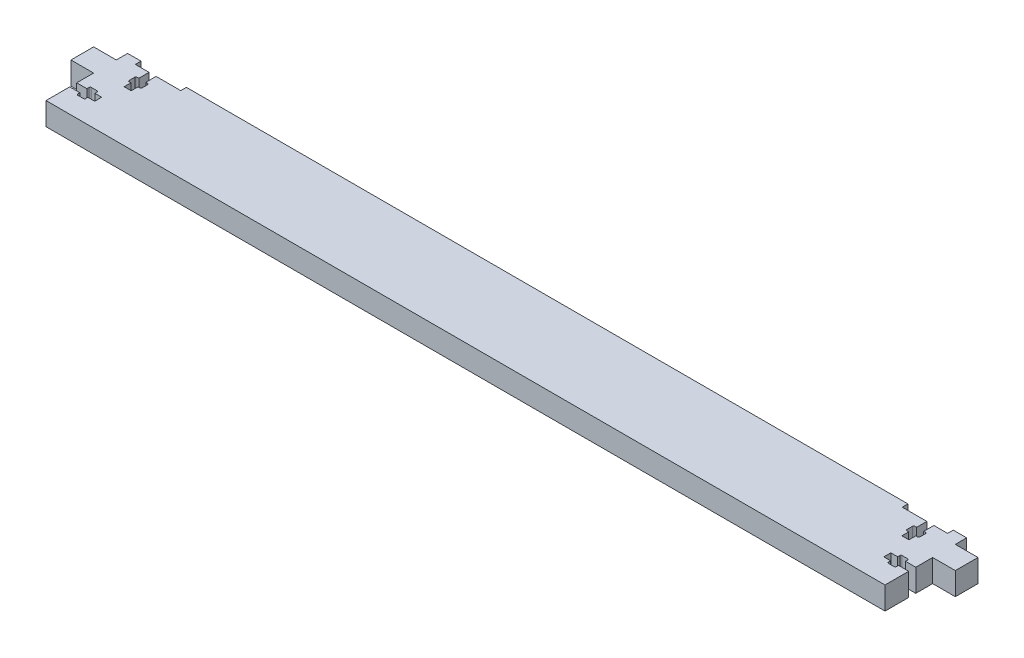
SolidWorks part; units mm, degrees
ref_plane "Front Plane" through (0, 0, 0) normal (0, 0, 1) x (1, 0, 0)
ref_plane "Top Plane" through (0, 0, 0) normal (0, 1, 0) x (1, 0, 0)
ref_plane "Right Plane" through (0, 0, 0) normal (1, 0, 0) x (0, 0, -1)
sketch "Sketch1" plane through (0, 0, 0) normal (0, 1, 0) x (1, 0, 0)
  line L0 (0, 18) -> (0, -18) construction
  line L1 (-185, 18) -> (0, 18)
  line L2 (-185, 18) -> (-185, 13)
  line L3 (-185, -18) -> (0, -18)
  line L4 (0, 18) -> (0, -18)
  line L5 (-185, 18) -> (0, 0) construction
  line L6 (-185, -18) -> (0, 0) construction
  line L7 (-185, 13) -> (-195, 13)
  line L8 (-195, 13) -> (-195, 3)
  line L9 (-195, 3) -> (-185, 3)
  line L10 (-185, 3) -> (-185, -18)
  point P0 (0, 0)
  dimension "D6" = 10
  dimension "D7" = 10
  dimension "D1" = 185
  dimension "D2" = 36
  dimension "D4" = 5
  dimension "D9" = 18
extrude "MainShape" add sketch "Sketch1" along normal blind 10 contours L2 L7 L8 L9 region at (-93.9423, 0, -0.1183)
sketch "Sketch15" plane through (0, 10, 0) normal (0, 1, 0) x (1, 0, 0)
  line L0 (-185, 18) -> (0, 18) construction
  line L1 (-159.1, 20.5) -> (-179.1, 20.5)
  line L2 (-159.1, 20.5) -> (-159.1, 15.5)
  line L3 (-159.1, 15.5) -> (-179.1, 15.5)
  line L4 (-179.1, 20.5) -> (-179.1, 15.5)
  line L5 (-159.1, 20.5) -> (-179.1, 15.5) construction
  line L6 (-159.1, 15.5) -> (-179.1, 20.5) construction
  line L7 (-185, 18) -> (-185, 13) construction
  point P0 (-169.1, 18)
  dimension "D1" = 20
  dimension "D2" = 2.5
  dimension "D3" = 15.9
extrude "Cut-Extrude6" cut sketch "Sketch15" against normal through all
sketch "Sketch2" plane through (0, 10, 0) normal (0, 1, 0) x (1, 0, 0)
  line L0 (-171.5, 15.5) -> (-171.5, 4.5) construction
  line L2 (-173.05, 15.5) -> (-173.05, 11)
  line L3 (-173.05, 11) -> (-173.85, 11)
  line L4 (-174.35, 10.5) -> (-174.35, 8)
  line L5 (-173.85, 7.5) -> (-173.05, 7.5)
  line L6 (-173.05, 7.5) -> (-173.05, 4.5)
  line L7 (-173.05, 4.5) -> (-169.95, 4.5)
  line L8 (-185, 18) -> (-185, 13) construction
  line L9 (-173.05, 15.5) -> (-169.95, 15.5)
  line L10 (-169.95, 7.5) -> (-169.95, 4.5)
  line L11 (-169.15, 7.5) -> (-169.95, 7.5)
  line L12 (-168.65, 10.5) -> (-168.65, 8)
  line L13 (-169.95, 11) -> (-169.15, 11)
  line L14 (-169.95, 15.5) -> (-169.95, 11)
  line L15 (-179.1, 15.5) -> (-159.1, 15.5) construction
  line L16 (-185, -6) -> (-174, -6) construction
  line L50 (-185, 3) -> (-185, -18) construction
  line L51 (-174, -7.55) -> (-174, -4.45)
  line L52 (-174, -4.45) -> (-177, -4.45)
  line L53 (-177, -4.45) -> (-177, -3.5)
  line L54 (-177.5, -3) -> (-180, -3)
  line L55 (-180.5, -3.5) -> (-180.5, -4.45)
  line L56 (-180.5, -4.45) -> (-185, -4.45)
  line L57 (-185, -4.45) -> (-185, -7.55)
  line L58 (-195, 13) -> (-195, 3) construction
  line L59 (-180.5, -7.55) -> (-185, -7.55)
  line L60 (-180.5, -8.5) -> (-180.5, -7.55)
  line L61 (-177.5, -9) -> (-180, -9)
  line L62 (-177, -7.55) -> (-177, -8.5)
  line L63 (-174, -7.55) -> (-177, -7.55)
  arc A0 (-174.35, 8) -> (-173.85, 7.5) centre (-173.85, 8) ccw
  arc A1 (-173.85, 11) -> (-174.35, 10.5) centre (-173.85, 10.5) ccw
  arc A2 (-169.15, 11) -> (-168.65, 10.5) centre (-169.15, 10.5) cw
  arc A3 (-168.65, 8) -> (-169.15, 7.5) centre (-169.15, 8) cw
  arc A16 (-177, -3.5) -> (-177.5, -3) centre (-177.5, -3.5) ccw
  arc A17 (-180, -3) -> (-180.5, -3.5) centre (-180, -3.5) ccw
  arc A18 (-180, -9) -> (-180.5, -8.5) centre (-180, -8.5) cw
  arc A19 (-177, -8.5) -> (-177.5, -9) centre (-177.5, -8.5) cw
  point P14 (-174.35, 7.5)
  point P17 (-174.35, 11)
  point P28 (-168.65, 11)
  point P29 (-168.65, 7.5)
  point P34 (-195, 8)
  point P45 (-177, -3)
  point P48 (-180.5, -3)
  dimension "D8" = 0.5
  dimension "D16" = 0.5
  dimension "D1" = 11
  dimension "D2" = 1.55
  dimension "D3" = 1.55
  dimension "D5" = 2.85
  dimension "D6" = 3.5
  dimension "D7" = 13.5
  dimension "D9" = 11
  dimension "D10" = 8
  dimension "D11" = 3.5
  dimension "D12" = 3
  dimension "D13" = 1.55
  dimension "D14" = 1.55
  dimension "D15" = 14
  dimension "D4" = 8
extrude "ScrewSlots" cut sketch "Sketch2" against normal through all
mirror "Mirror1" about plane through (0, 0, 0) normal (1, 0, 0) of "Cut-Extrude6", "MainShape", "ScrewSlots"
sketch "Sketch6" [suppressed] plane through (0, 10, 0) normal (0, 1, 0) x (1, 0, 0)
  line L0 (0, -18) -> (0, -48) construction
  line L2 (-185, -18) -> (185, -18) construction
  line L3 (90, -48) -> (-90, -48)
  line L4 (-90, -48) -> (-120, -18)
  line L5 (90, -48) -> (120, -18)
  line L6 (-120, -18) -> (120, -18)
  dimension "D1" = 135
  dimension "D2" = 30
  dimension "D3" = 90
extrude "Boss-Extrude1" [suppressed] add sketch "Sketch6" against normal through all
sketch "Sketch8" [suppressed] plane through (0, 10, 0) normal (0, 1, 0) x (1, 0, 0)
  line L0 (-71.5, 4.8833) -> (-77.5, 4.8833) construction
  line L1 (-77, -1.6167) -> (-72, -1.6167)
  line L2 (-78, -0.6167) -> (-78, 4.3833)
  line L3 (-77, 5.3833) -> (-72, 5.3833)
  line L4 (-71, -0.6167) -> (-71, 4.3833)
  line L5 (-78, -1.6167) -> (-71, 5.3833) construction
  line L6 (-78, 5.3833) -> (-71, -1.6167) construction
  line L7 (-71.5, -1.1167) -> (-71.5, 4.8833) construction
  circle A0 centre (-74.5, -34.7667) radius 6.5
  circle A1 centre (-74.5, -15.8167) radius 5.5
  arc A2 (-77, -1.6167) -> (-78, -0.6167) centre (-77, -0.6167) cw
  circle A3 centre (-74.5, -34.7667) radius 6 construction
  circle A4 centre (-74.5, -15.8167) radius 3.5 construction
  arc A5 (-72, -1.6167) -> (-71, -0.6167) centre (-72, -0.6167) ccw
  arc A6 (-72, 5.3833) -> (-71, 4.3833) centre (-72, 4.3833) cw
  arc A7 (-78, 4.3833) -> (-77, 5.3833) centre (-77, 4.3833) cw
  point P6 (-74.5, 1.8833)
  dimension "D1" = 0.5
  dimension "D2" = 2
  dimension "D3" = 0.5
  dimension "D5" = 1
  dimension "D4" = 0.5
extrude "Cut-Extrude2" [suppressed] cut sketch "Sketch8" against normal through all
sketch "Sketch7" [suppressed] plane through (0, 10, 0) normal (0, 1, 0) x (1, 0, 0)
  circle A0 centre (60.5, -43.0167) radius 1.45
  circle A1 centre (-84.5, -43.0167) radius 1.45
  circle A2 centre (-84.5, 6.4833) radius 1.45
  circle A3 centre (60.5, 6.4833) radius 1.45
  dimension "D1" = 2.9
  dimension "D2" = 2.9
  dimension "D3" = 2.9
  dimension "D4" = 2.9
extrude "Cut-Extrude1" [suppressed] cut sketch "Sketch7" against normal through all
sketch "Sketch9" [suppressed] plane through (0, 10, 0) normal (0, 1, 0) x (1, 0, 0)
  line L0 (0, 7.2333) -> (0, -32.7667) construction
  line L1 (48.5, 7.2333) -> (-48.5, 7.2333) construction
  line L2 (-48.5, -32.7667) -> (48.5, -32.7667) construction
  line L3 (-48.5, -12.7667) -> (48.5, -12.7667) construction
  line L4 (-48.5, 7.2333) -> (-48.5, -32.7667) construction
  line L5 (48.5, -32.7667) -> (48.5, 7.2333) construction
  line L7 (-49, -33.2667) -> (49, -33.2667)
  line L8 (-49, -33.2667) -> (-49, 7.7333)
  line L9 (-49, 7.7333) -> (49, 7.7333)
  line L10 (49, -33.2667) -> (49, 7.7333)
  line L11 (-49, -33.2667) -> (49, 7.7333) construction
  line L12 (-49, 7.7333) -> (49, -33.2667) construction
  point P12 (0, -12.7667)
  dimension "D1" = 0.5
  dimension "D2" = 0.5
extrude "Cut-Extrude3" [suppressed] cut sketch "Sketch9" against normal through all and the other way through all
sketch "Sketch10" [suppressed] plane through (0, 10, 0) normal (0, 1, 0) x (1, 0, 0)
  line L0 (20, -39.2667) -> (20, -40.7667) construction
  line L1 (40, -39.2667) -> (0, -39.2667) construction
  line L2 (0, -40.7667) -> (40, -40.7667) construction
  line L3 (0, -40.0167) -> (40, -40.0167) construction
  line L4 (0, -39.2667) -> (0, -40.7667) construction
  line L5 (40, -40.7667) -> (40, -39.2667) construction
  line L7 (-0.2, -40.9667) -> (40.2, -40.9667)
  line L8 (-0.2, -40.9667) -> (-0.2, -39.0667)
  line L9 (-0.2, -39.0667) -> (40.2, -39.0667)
  line L10 (40.2, -40.9667) -> (40.2, -39.0667)
  line L11 (-0.2, -40.9667) -> (40.2, -39.0667) construction
  line L12 (-0.2, -39.0667) -> (40.2, -40.9667) construction
  point P12 (20, -40.0167)
  dimension "D1" = 0.2
  dimension "D2" = 0.2
extrude "Cut-Extrude4" [suppressed] cut sketch "Sketch10" against normal through all
sketch "Sketch12" [suppressed] plane through (0, 0, 0) normal (0, -1, 0) x (-1, 0, 0)
  line L1 (81.4, -9.8167) -> (67.6, -9.8167)
  line L2 (81.4, -9.8167) -> (81.4, -21.8167)
  line L3 (81.4, -21.8167) -> (67.6, -21.8167)
  line L4 (67.6, -9.8167) -> (67.6, -21.8167)
  line L5 (81.4, -9.8167) -> (67.6, -21.8167) construction
  line L6 (81.4, -21.8167) -> (67.6, -9.8167) construction
  point P0 (74.5, -15.8167)
  dimension "D1" = 13.8
  dimension "D2" = 12
extrude "PotentiometerAdjustment" [suppressed] cut sketch "Sketch12" against normal through all
sketch "Sketch11" plane through (0, 0, 0) normal (0, -1, 0) x (1, 0, 0)
  line L1 (-149, 0.5) -> (-167, 0.5)
  line L2 (-147, 2.5) -> (-147, 9.5)
  line L3 (-149, 11.5) -> (-167, 11.5)
  line L4 (-169, 2.5) -> (-169, 9.5)
  line L5 (-147, 0.5) -> (-169, 11.5) construction
  line L6 (-147, 11.5) -> (-169, 0.5) construction
  line L7 (173.05, -4.5) -> (169.95, -4.5) construction
  line L8 (-174, 7.55) -> (-174, 4.45) construction
  arc A0 (-147, 9.5) -> (-149, 11.5) centre (-149, 9.5) ccw
  arc A1 (-167, 11.5) -> (-169, 9.5) centre (-167, 9.5) ccw
  arc A2 (-167, 0.5) -> (-169, 2.5) centre (-167, 2.5) cw
  arc A3 (-149, 0.5) -> (-147, 2.5) centre (-149, 2.5) ccw
  point P0 (-158, 6)
  dimension "D3" = 2
  dimension "D1" = 22
  dimension "D2" = 11
  dimension "D4" = 5
  dimension "D5" = 5
extrude "LCDCableCutout" [suppressed] cut sketch "Sketch11" against normal through all
sketch "Sketch13" plane through (0, 10, 0) normal (0, 1, 0) x (1, 0, 0)
  line L0 (0, 18) -> (0, -18) construction
  line L1 (-169.95, 18) -> (169.95, 18) construction
  line L2 (-185, -18) -> (185, -18) construction
  line L3 (120, 18) -> (-120, 18) construction
  line L4 (120, 8) -> (-120, 8)
  line L5 (120, 28) -> (-120, 28)
  arc A0 (120, 8) -> (120, 28) centre (120, 18) ccw
  arc A1 (-120, 28) -> (-120, 8) centre (-120, 18) ccw
  point P8 (0, 18)
  dimension "D2" = 120
  dimension "D1" = 10
extrude "Cut-Extrude5" [suppressed] cut sketch "Sketch13" against normal through all
sketch "Sketch14" plane through (0, 10, 0) normal (0, 1, 0) x (1, 0, 0)
  line L1 (-169.95, 18) -> (169.95, 18) construction
  line L3 (-156.5, 18) -> (-156.5, 28) construction
  line L4 (-161.5, 18) -> (-151.5, 18)
  line L5 (-161.5, 18) -> (-161.5, 28)
  line L6 (-161.5, 28) -> (-151.5, 28)
  line L7 (-151.5, 18) -> (-151.5, 28)
  line L8 (-173.05, 4.5) -> (-169.95, 4.5) construction
  line L9 (154, 18) -> (154, 28) construction
  line L10 (149, 18) -> (149, 28)
  line L11 (159, 28) -> (149, 28)
  line L12 (159, 18) -> (159, 28)
  line L13 (159, 18) -> (149, 18)
  point P12 (-171.5, 4.5)
  dimension "D1" = 10
  dimension "D2" = 10
  dimension "D3" = 15
extrude "Boss-Extrude3" [suppressed] add sketch "Sketch14" against normal through all
equation "\"Y-ROD-SPACING\"=75"
equation "\"Y-BED-OFFSET\"=2"
equation "\"Y-BED-ROD-INSET\"=3.5"
equation "\"T-SLOT-NUT-FILLET-RADIUS\"=0.5"
equation "\"T-SLOT-SCREW-SHAFT-RADIUS\"=1.55"
equation "\"T-SLOT-SCREW-SHAFT-CUTOUT-LENGTH\"=11"
equation "\"T-SLOT-NUT-DEPTH\"=3.5"
equation "\"T-SLOT-NUT-WIDTH\"=2.85"
equation "\"T-SLOT-NUT-END-DISTANCE\"=8"
equation "\"ACRYLIC-TAB-CUTOUT-SIZE\"=\"ACRYLIC-THICKNESS\"+\"ACRYLIC-TAB-TOLERANCE\"*2"
equation "\"ACRYLIC-M3-HOLE\"=2.9"
equation "\"SMOOTHROD-CAP-SCREW-DISTANCE\"=20"
equation "\"D2@Sketch2\"=\"T-SLOT-SCREW-SHAFT-RADIUS\""
equation "\"D1@Sketch2\"=\"T-SLOT-SCREW-SHAFT-CUTOUT-LENGTH\""
equation "\"D6@Sketch2\"=\"T-SLOT-NUT-DEPTH\""
equation "\"D5@Sketch2\"=\"T-SLOT-NUT-WIDTH\""
equation "\"D3@Sketch2\"=\"T-SLOT-SCREW-SHAFT-RADIUS\""
equation "\"D8@Sketch2\"=\"T-SLOT-NUT-FILLET-RADIUS\""
equation "\"D4@Sketch2\"=\"T-SLOT-NUT-END-DISTANCE\""
equation "\"D11@Sketch2\"=\"T-SLOT-NUT-DEPTH\""
equation "\"D10@Sketch2\"=\"T-SLOT-NUT-END-DISTANCE\""
equation "\"D13@Sketch2\"=\"T-SLOT-SCREW-SHAFT-RADIUS\""
equation "\"D14@Sketch2\"=\"T-SLOT-SCREW-SHAFT-RADIUS\""
equation "\"D16@Sketch2\"=\"T-SLOT-NUT-FILLET-RADIUS\""
equation "\"D9@Sketch2\"=\"T-SLOT-SCREW-SHAFT-CUTOUT-LENGTH\""
equation "\"ACRYLIC-TAB-WIDTH\"=\"ACRYLIC-THICKNESS\""
equation "\"D6@Sketch1\"=\"ACRYLIC-TAB-WIDTH\""
equation "\"D7@Sketch1\"=\"ACRYLIC-TAB-WIDTH\""
equation "\"FRAME-WIDTH-INNER\"=370"
equation "\"D1@Sketch1\"=\"FRAME-WIDTH-INNER\"/2"
equation "\"X-ROD-SPACING\"=45"
equation "\"Z-ROD-SPACING\"=17.5"
equation "\"ACRYLIC-THICKNESS\"=10"
equation "\"ACRYLIC-THICKNESS2\"=4.5"
equation "\"NEMA17-HOLE-SPACING\"=31"
equation "\"NEMA17-CENTRAL-CUTOUT\"=22.5"
equation "\"Z-BRACKET-REACH\"=55"
equation "\"TOP-BRACKET-SPACING\"=40"
equation "\"SMOOTHROD-X-LENGTH\"=350"
equation "\"SMOOTHROD-Y-LENGTH\"=350"
equation "\"SMOOTHROD-Z-LENGTH\"=350"
equation "\"SMOOTHROD-TIGHTENING-HEADROOM\"=.25"
equation "\"LEADSCREW-Z-LENGTH\"=300"
equation "\"SCREW-LENGTH-FRAME\"=\"ACRYLIC-THICKNESS\" + 10"
equation "\"SCREW-HEAD-RADIUS\"=6"
equation "\"PRINTED-X-SMOOTHROD-DIAMETER\"=9.0"
equation "\"PRINTED-X-SMOOTHROD-CUTOUT\"=10"
equation "\"PRINTED-X-BASE-HEIGHT\"=10"
equation "\"PRINTED-LM8UU-CUTOUT-SIZE\"=15.5"
equation "\"PRINTED-LM8UU-CUTOUT-LENGTH\"=24.5"
equation "\"PRINTED-X-IDLER-HEIGHT\"=16"
equation "\"PSU-MOUNTING-WIDTH\"=95"
equation "\"PSU-MOUNTING-HEIGHT\"=177"
equation "\"D1@MainShape\"=\"ACRYLIC-THICKNESS\""
equation "\"Y-BELT-TO-ROD-DISTANCE\"=20"
equation "\"SPOOL-HOLDER-ROD-SPACING\"=150"
equation "\"Z-ROD-INSET\"=13.5"
equation "\"D7@Sketch2\"=\"Z-ROD-INSET\""
equation "\"D1@Sketch7\"=\"ACRYLIC-M3-HOLE\""
equation "\"D2@Sketch7\"=\"ACRYLIC-M3-HOLE\""
equation "\"D3@Sketch7\"=\"ACRYLIC-M3-HOLE\""
equation "\"D4@Sketch7\"=\"ACRYLIC-M3-HOLE\""
equation "\"Y-BED-SCREW-SPACING\"=209"
equation "\"Y-BED-SCREW-CUTOUT-SLOT-HEIGHT\"=2"
equation "\"ACRYLIC-TAB-TOLERANCE\"=-.05"
equation "\"SCREW-LENGTH-MOTOR\"=\"ACRYLIC-THICKNESS\" + 5"
equation "\"SCREW-LENGTH-EXTRUDER\"=28"
equation "\"PRINTED-M3-HOLE\"=3.5"
equation "\"PRINTED-M3-NUT-AF\"=6.25"
equation "\"ACRYLIC-X-CARRIAGE-WIDTH\"=55"
equation "\"ACRYLIC-X-CARRIAGE-HEIGHT\"=75"
equation "\"ACRYLIC-X-CARRIAGE-LM8UU-CUTOUT-WIDTH\"=24.25"
equation "\"ACRYLIC-X-CARRIAGE-LM8UU-CUTOUT-HEIGHT\"=11.0"
equation "\"ACRYLIC-X-CARRIAGE-SCREW-SPACING-X\"=15"
equation "\"ACRYLIC-X-CARRIAGE-SCREW-SPACING-Y\"=33"
equation "\"ACRYLIC-X-CARRIAGE-CENTER-TAB-SPACING\"=14"
equation "\"ACRYLIC-X-CARRIAGE-EXTRUDER-OFFSET\"=26"
equation "\"ACRYLIC-X-CARRIAGE-EXTRUDER-ANGLE\"=90"
equation "\"ACRYLIC-X-CARRIAGE-EXTRUDER-SHELF-DEPTH\"=\"ACRYLIC-X-CARRIAGE-EXTRUDER-OFFSET\" + 28"
equation "\"ACRYLIC-X-CARRIAGE-EXTRUDER-BRACE-SPACING\"=23"
equation "\"ACRYLIC-X-CARRIAGE-EXTRUDER-BRACE-TAB-OFFSET\"=20"
equation "\"ACRYLIC-X-CARRIAGE-EXTRUDER-BRACE-HEIGHT\"=35"
equation "\"ACRYLIC-X-CARRIAGE-EXTRUDER-BRACE-SCREW-SPACING\"=22"
equation "\"ACRYLIC-X-CARRIAGE-DUAL-WIDTH-MULTIPLIER\"=1.65"
equation "\"ACRYLIC-X-CARRIAGE-DUAL-HOTEND-SPACING\"=42"
equation "\"ACRYLIC-X-CARRIAGE-DUAL-WIDTH\"=75"
equation "\"ACRYLIC-X-CARRIAGE-DUAL-HOTEND-SEPARATION\"=36"
equation "\"ACRYLIC-X-CARRIAGE-DUAL-MOUNT-PLATE-DEPTH\"=75"
equation "\"ACRYLIC-X-CARRIAGE-DUAL-MOUNT-BRACE-WIDTH\"=33"
equation "\"ACRYLIC-X-CARRIAGE-DUAL-MOUNT-SCREW-WIDTH\"=40"
equation "\"BLOWER-FAN-WIDTH\"=15"
equation "\"D1@Sketch14\"=\"ACRYLIC-TAB-WIDTH\""
equation "\"D2@Sketch14\"=\"ACRYLIC-THICKNESS\""
equation "\"D3@Sketch15\"=\"Z-ROD-INSET\"+2.4"
